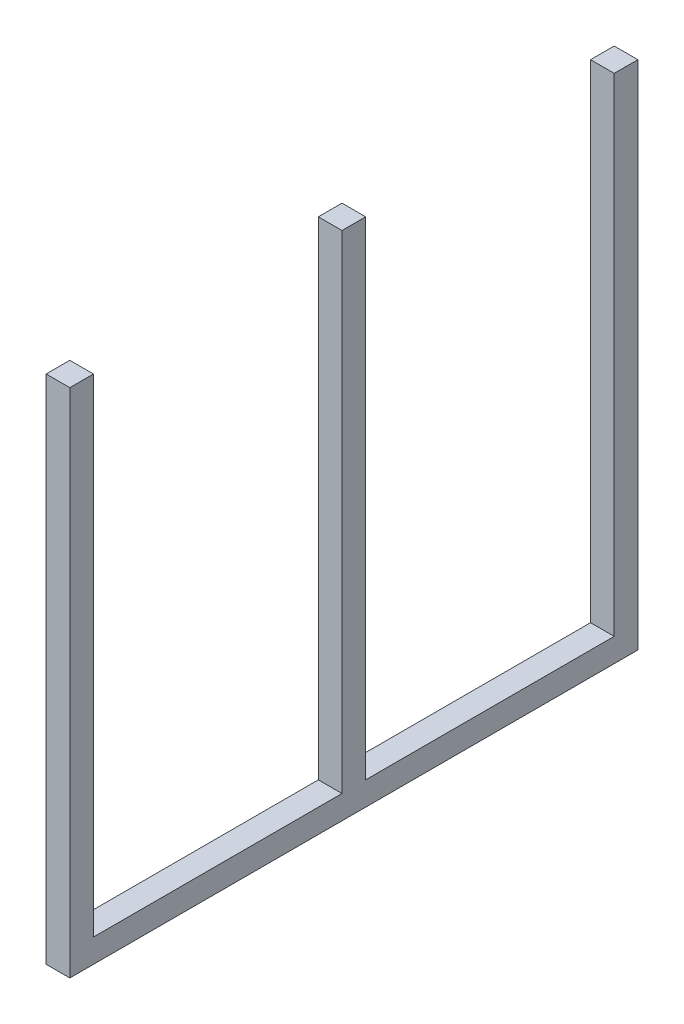
SolidWorks part; units mm, degrees
ref_plane "Front Plane" through (0, 0, 0) normal (0, 0, 1) x (1, 0, 0)
ref_plane "Top Plane" through (0, 0, 0) normal (0, 1, 0) x (1, 0, 0)
ref_plane "Right Plane" through (0, 0, 0) normal (1, 0, 0) x (0, 0, -1)
sketch "Sketch1" plane through (0, 0, 0) normal (0, 0, 1) x (1, 0, 0)
  line L1 (15.875, -15.875) -> (-15.875, -15.875)
  line L2 (15.875, -15.875) -> (15.875, 15.875)
  line L3 (15.875, 15.875) -> (-15.875, 15.875)
  line L4 (-15.875, -15.875) -> (-15.875, 15.875)
  line L5 (15.875, -15.875) -> (-15.875, 15.875) construction
  line L6 (15.875, 15.875) -> (-15.875, -15.875) construction
  line L7 (12.065, -12.065) -> (-12.065, -12.065)
  line L8 (12.065, -12.065) -> (12.065, 12.065)
  line L9 (12.065, 12.065) -> (-12.065, 12.065)
  line L10 (-12.065, -12.065) -> (-12.065, 12.065)
  line L11 (12.065, -12.065) -> (-12.065, 12.065) construction
  line L12 (12.065, 12.065) -> (-12.065, -12.065) construction
  point P0 (0, 0)
  point P6 (0, 0)
  dimension "D1" = 31.75
  dimension "D2" = 3.81
extrude "Boss-Extrude1" add sketch "Sketch1" along normal blind 762
sketch "Sketch14" plane through (0, -15.875, 0) normal (0, -1, 0) x (1, 0, 0)
  line L0 (15.875, 762) -> (15.875, 0) construction
  line L1 (15.875, 762) -> (-15.875, 762)
  line L2 (15.875, 762) -> (15.875, 730.25)
  line L3 (15.875, 730.25) -> (-15.875, 730.25)
  line L4 (-15.875, 762) -> (-15.875, 730.25)
  line L5 (12.7, 733.425) -> (-12.7, 733.425)
  line L6 (12.7, 733.425) -> (12.7, 758.825)
  line L7 (12.7, 758.825) -> (-12.7, 758.825)
  line L8 (-12.7, 733.425) -> (-12.7, 758.825)
  line L9 (12.7, 733.425) -> (-12.7, 758.825) construction
  line L10 (12.7, 758.825) -> (-12.7, 733.425) construction
  line L11 (-15.875, 762) -> (15.875, 762) construction
  point P4 (0, 746.125)
  point P10 (0, 762)
  point P11 (-15.875, 746.125)
  point P12 (0, 0)
  point P13 (0, 0)
  point P14 (0, 0)
  point P15 (15.875, 728.1561)
  dimension "D1" = 31.75
  dimension "D2" = 25.4
extrude "Boss-Extrude2" add sketch "Sketch14" against normal blind 685.8
extrude "Boss-Extrude3" add sketch "Sketch14<2>" against normal blind 2.54 contours L8 L5 L6 L7 region at (0, -15.875, 746.125)
sketch "Sketch14<2>" plane through (0, -15.875, 0) normal (0, -1, 0) x (1, 0, 0) same geometry as "Sketch14"
extrude "Boss-Extrude6" add sketch "Sketch14<3>" against normal blind 2.54 from offset 683.26 contours L8 L5 L6 L7 region at (0, -15.875, 746.125) offset against normal yes
sketch "Sketch14<3>" plane through (0, -15.875, 0) normal (0, -1, 0) x (1, 0, 0) same geometry as "Sketch14"
extrude "Boss-Extrude4" add sketch "Sketch1<2>" along normal blind 2.54 contours L10 L7 L8 L9 region at (0, 0, 0)
sketch "Sketch1<2>" plane through (0, 0, 0) normal (0, 0, 1) x (1, 0, 0) same geometry as "Sketch1"
extrude "Boss-Extrude5" add sketch "Sketch1<3>" along normal blind 2.54 from offset 759.46 contours L10 L7 L8 L9 region at (0, 0, 0)
sketch "Sketch1<3>" plane through (0, 0, 0) normal (0, 0, 1) x (1, 0, 0) same geometry as "Sketch1"
pattern_linear "LPattern4" count 3 spacing 365.125 along (0, 0, -1) of "Boss-Extrude2", "Boss-Extrude3", "Boss-Extrude6"
